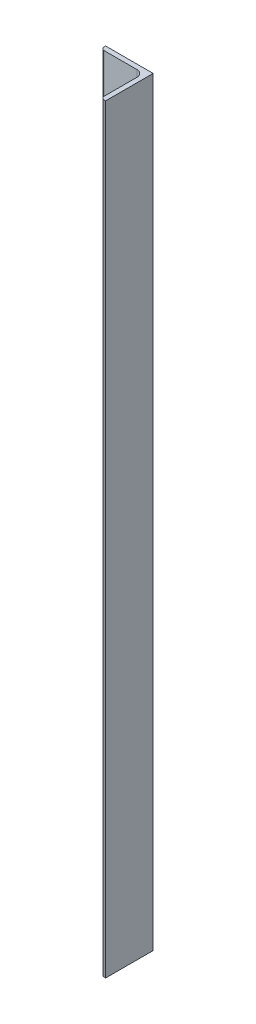
SolidWorks part; units mm, degrees
ref_plane "Front Plane" through (0, 0, 0) normal (0, 0, 1) x (1, 0, 0)
ref_plane "Top Plane" through (0, 0, 0) normal (0, 1, 0) x (1, 0, 0)
ref_plane "Right Plane" through (0, 0, 0) normal (1, 0, 0) x (0, 0, -1)
sketch "Sketch1" plane through (0, 0, 0) normal (0, 1, 0) x (1, 0, 0)
  line L6 (0, 0) -> (-50, 0)
  line L10 (0, 0) -> (0, -50)
  line L11 (0, -50) -> (-1.5, -50)
  line L12 (-50, 0) -> (-50, -1.5)
  line L15 (-46.5, -5) -> (-12, -5)
  line L16 (-5, -46.5) -> (-5, -12)
  arc A8 (-12, -5) -> (-5, -12) centre (-12, -12) cw
  arc A9 (-1.5, -50) -> (-5, -46.5) centre (-1.5, -46.5) cw
  arc A10 (-50, -1.5) -> (-46.5, -5) centre (-46.5, -1.5) ccw
  dimension "D4" = 5
  dimension "D5" = 7
  dimension "D6" = 3.5
  dimension "D1" = 50
  dimension "D2" = 50
  dimension "D3" = 5
extrude "Boss-Extrude1" add sketch "Sketch1" along normal mid plane 800
